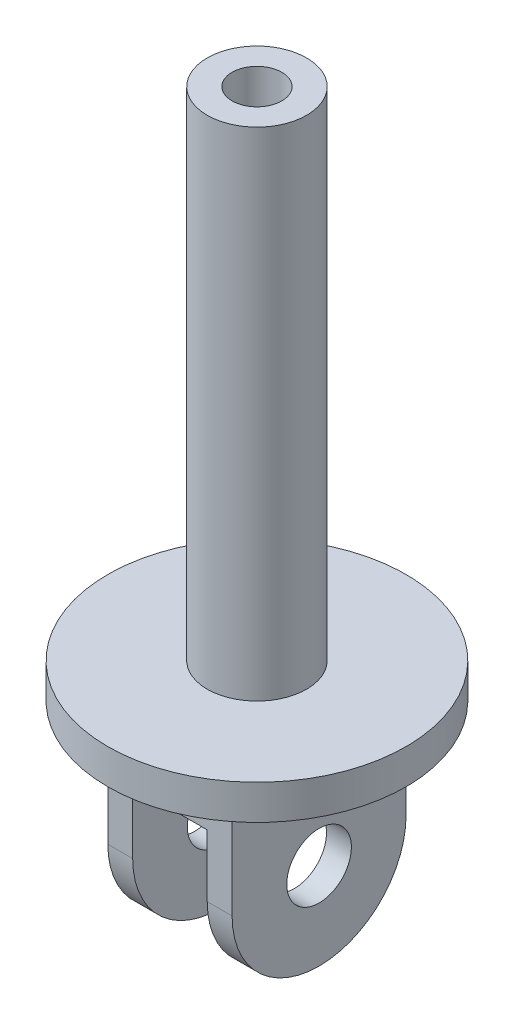
SolidWorks part; units mm, degrees
ref_plane "Front Plane" through (0, 0, 0) normal (0, 0, 1) x (1, 0, 0)
ref_plane "Top Plane" through (0, 0, 0) normal (0, 1, 0) x (1, 0, 0)
ref_plane "Right Plane" through (0, 0, 0) normal (1, 0, 0) x (0, 0, -1)
sketch "Sketch1" plane through (0, 0, 0) normal (0, 1, 0) x (1, 0, 0)
  line L1 (-12.5, 17.5) -> (12.5, 17.5)
  line L2 (-12.5, 17.5) -> (-12.5, -17.5)
  line L3 (-12.5, -17.5) -> (12.5, -17.5)
  line L4 (12.5, 17.5) -> (12.5, -17.5)
  line L5 (-12.5, 17.5) -> (12.5, -17.5) construction
  line L6 (-12.5, -17.5) -> (12.5, 17.5) construction
  point P0 (0, 0)
  dimension "D1" = 25
  dimension "D2" = 35
extrude "Boss-Extrude1" add sketch "Sketch1" along normal blind 40
fillet "Fillet1" 2 edges at (0, 0, 17.5) (0, 0, -17.5) type full round first side face at (0, 20, 17.5) second side face at (0, 20, -17.5) middle face at (0, 0, 0)
sketch "Sketch2" plane through (0, 0, 0) normal (0, 1, 0) x (1, 0, 0)
  line L0 (12.5, 17.5) -> (-12.5, 17.5) construction
  line L1 (-7.5, -17.5) -> (7.5, -17.5)
  line L2 (-7.5, -17.5) -> (-7.5, 17.5)
  line L3 (-7.5, 17.5) -> (7.5, 17.5)
  line L4 (7.5, -17.5) -> (7.5, 17.5)
  line L5 (-7.5, -17.5) -> (7.5, 17.5) construction
  line L6 (-7.5, 17.5) -> (7.5, -17.5) construction
  point P0 (0, 0)
  dimension "D1" = 15
extrude "Cut-Extrude1" cut sketch "Sketch2" along normal blind 30
sketch "Sketch3" plane through (-12.5, 0, 0) normal (-1, 0, 0) x (0, 0, 1)
  circle A0 centre (0, 17.5) radius 6.5
  dimension "D1" = 13
extrude "Cut-Extrude2" cut sketch "Sketch3" against normal blind 30
sketch "Sketch5" plane through (0, 40, 0) normal (0, 1, 0) x (1, 0, 0)
  circle A0 centre (0, 0) radius 30
  dimension "D1" = 60
extrude "Boss-Extrude2" add sketch "Sketch5" along normal blind 7
sketch "Sketch6" plane through (0, 47, 0) normal (0, 1, 0) x (1, 0, 0)
  circle A0 centre (0, 0) radius 10
  circle A1 centre (0, 0) radius 5
  dimension "D1" = 20
  dimension "D2" = 10
extrude "Boss-Extrude3" add sketch "Sketch6" along normal blind 100
